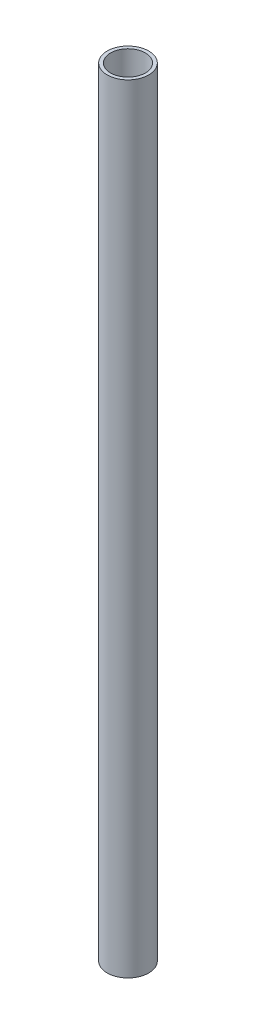
SolidWorks part; units mm, degrees
ref_plane "Front Plane" through (0, 0, 0) normal (0, 0, 1) x (1, 0, 0)
ref_plane "Top Plane" through (0, 0, 0) normal (0, 1, 0) x (1, 0, 0)
ref_plane "Right Plane" through (0, 0, 0) normal (1, 0, 0) x (0, 0, -1)
sketch "Sketch1" plane through (0, 0, 0) normal (0, 1, 0) x (1, 0, 0)
  circle A0 centre (0, 0) radius 7.75
  circle A1 centre (0, 0) radius 6.5
  dimension "D1" = 15.5
  dimension "D2" = 13
extrude "Boss-Extrude1" add sketch "Sketch1" along normal blind 270
extrude "Boss-Extrude3" add sketch "Sketch1<2>" against normal blind 20.4764
sketch "Sketch1<2>" plane through (0, 0, 0) normal (0, 1, 0) x (1, 0, 0) same geometry as "Sketch1"
